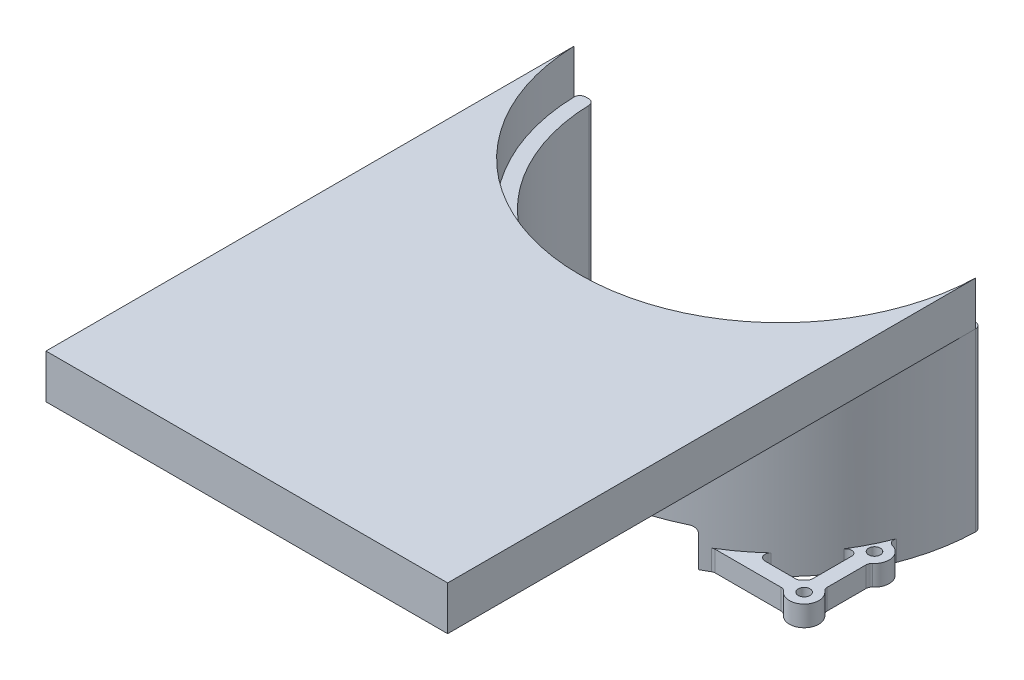
SolidWorks part; units mm, degrees
ref_plane "Front" through (0, 0, 0) normal (0, 0, 1) x (1, 0, 0)
ref_plane "Top" through (0, 0, 0) normal (0, 1, 0) x (1, 0, 0)
ref_plane "Right" through (0, 0, 0) normal (1, 0, 0) x (0, 0, -1)
sketch "Sketch1" plane through (0, 0, 0) normal (0, 1, 0) x (1, 0, 0)
  line L0 (63.4901, 0) -> (68.5, 0)
  line L1 (61.5003, -36.3303) -> (61.5003, -51.6697)
  line L2 (66.4997, -51.6697) -> (66.4997, -36.3303)
  line L3 (59.6699, -53.5) -> (42.7785, -53.5)
  line L4 (59.6699, -58.5) -> (35.6371, -58.5)
  line L5 (-66.4997, -51.6697) -> (-66.4997, -36.3303)
  line L6 (-68.5, 0) -> (-63.4901, 0)
  line L7 (0, 0) -> (0, -50000) construction
  line L12 (-59.6699, -58.5) -> (-35.6371, -58.5)
  line L14 (-59.6699, -53.5) -> (-42.7785, -53.5)
  line L16 (-61.5003, -36.3303) -> (-61.5003, -51.6697)
  arc A0 (-63.4901, 0) -> (63.4901, 0) centre (0, 0) ccw
  arc A5 (-68.5, 0) -> (-62.9018, -27.1221) centre (0, 0) ccw
  circle A6 centre (-64, -32) radius 2
  arc A7 (-62.9018, -27.1221) -> (-66.4997, -36.3303) centre (-64, -32) ccw
  circle A8 centre (64, -32) radius 2
  arc A9 (66.4997, -36.3303) -> (62.9018, -27.1221) centre (64, -32) ccw
  circle A10 centre (64, -56) radius 2
  arc A11 (61.5003, -51.6697) -> (59.6699, -53.5) centre (64, -56) ccw
  circle A12 centre (-64, -56) radius 2
  arc A13 (-59.6699, -53.5) -> (-61.5003, -51.6697) centre (-64, -56) ccw
  arc A14 (-35.6371, -58.5) -> (35.6371, -58.5) centre (0, 0) ccw
  arc A15 (-59.4388, -34.0482) -> (-42.7785, -53.5) centre (0, 0) ccw
  arc A16 (-61.5003, -36.3303) -> (-59.4388, -34.0482) centre (-64, -32) ccw
  arc A17 (-66.4997, -51.6697) -> (-59.6699, -58.5) centre (-64, -56) ccw
  arc A18 (59.6699, -58.5) -> (66.4997, -51.6697) centre (64, -56) ccw
  arc A19 (42.7785, -53.5) -> (59.4388, -34.0482) centre (0, 0) ccw
  arc A20 (59.4388, -34.0482) -> (61.5003, -36.3303) centre (64, -32) ccw
  arc A21 (62.9018, -27.1221) -> (68.5, 0) centre (0, 0) ccw
  point P6 (0, 0)
  point P45 (0, -32)
extrude "Boss-Extrude1" add sketch "Sketch1" along normal blind 60
sketch "Sketch2" plane through (0, 60, 0) normal (0, 1, 0) x (1, 0, 0)
  circle A0 centre (0, 0) radius 68.5
  circle A1 centre (0, 0) radius 90.0412
extrude "Cut-Extrude1" cut sketch "Sketch2" against normal blind 53
ref_plane "Plane1" through (0, 60, 68.5) normal (0, 0, 1) x (1, 0, 0)
sketch "Sketch3" plane through (0, 60, 68.5) normal (0, 0, 1) x (1, 0, 0)
  line L1 (-32.3393, -72.711) -> (32.3393, -72.711)
  line L2 (-32.3393, -72.711) -> (-32.3393, -47.289)
  line L3 (-32.3393, -47.289) -> (32.3393, -47.289)
  line L4 (32.3393, -72.711) -> (32.3393, -47.289)
  line L5 (-32.3393, -72.711) -> (32.3393, -47.289) construction
  line L6 (-32.3393, -47.289) -> (32.3393, -72.711) construction
  point P0 (0, -60)
extrude "Cut-Extrude2" cut sketch "Sketch3" against normal blind 55
fillet "Fillet1" radius 2 26 edges at (-32.3393, 12.711, 57.5112) (32.3393, 12.711, 57.5112) (68.5, 30, 0) (63.4901, 30, 0) (-68.5, 30, 0) (-63.4901, 30, 0) (-62.9018, 3.5, 27.1221) (-59.4388, 3.5, 34.0482) (-61.5003, 3.5, 36.3303) (-61.5003, 3.5, 51.6697) (-59.6699, 3.5, 53.5) (-42.7785, 3.5, 53.5) (-35.6371, 3.5, 58.5) (-66.4997, 3.5, 51.6697) (-66.4997, 3.5, 36.3303) (-59.6699, 3.5, 58.5) (35.6371, 3.5, 58.5) (42.7785, 3.5, 53.5) (59.6699, 3.5, 53.5) (61.5003, 3.5, 51.6697) (61.5003, 3.5, 36.3303) (59.4388, 3.5, 34.0482) (62.9018, 3.5, 27.1221) (66.4997, 3.5, 36.3303) (59.6699, 3.5, 58.5) (66.4997, 3.5, 51.6697)
sketch "Sketch4" plane through (0, 60, 0) normal (0, 1, 0) x (1, 0, 0)
  line L0 (-68.469, -2.0602) -> (-68.469, -182.0602)
  line L1 (-68.469, -182.0602) -> (68.5, -182.0602)
  line L2 (68.5, -182.0602) -> (68.469, -2.0602)
  arc A0 (-68.469, -2.0602) -> (68.469, -2.0602) centre (0, 0) ccw
extrude "Boss-Extrude2" add sketch "Sketch4" along normal blind 15
